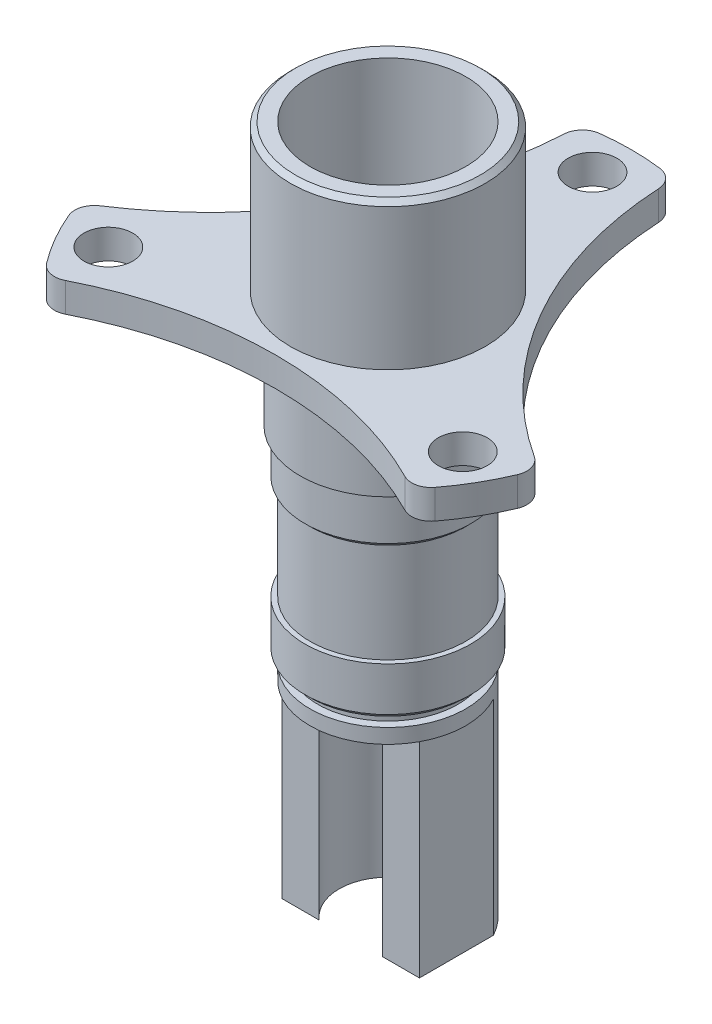
SolidWorks part; units mm, degrees
ref_plane "前视基准面" through (0, 0, 0) normal (0, 0, 1) x (1, 0, 0)
ref_plane "上视基准面" through (0, 0, 0) normal (0, 1, 0) x (1, 0, 0)
ref_plane "右视基准面" through (0, 0, 0) normal (1, 0, 0) x (0, 0, -1)
sketch "草图2" plane through (0, 0, 0) normal (0, 0, 1) x (1, 0, 0)
  line L0 (0, 0) -> (0, 49.7)
  line L1 (0, 49.7) -> (10, 49.7)
  line L3 (10, 34.7) -> (25, 34.7)
  line L4 (25, 34.7) -> (25, 31.7)
  line L5 (25, 31.7) -> (9, 31.7)
  line L9 (9, 22.7) -> (8.5, 22.7)
  line L10 (8.5, 22.7) -> (8.5, 18.2)
  line L11 (8.5, 18.2) -> (8, 18.2)
  line L12 (8, 18.2) -> (8, 7.5)
  line L13 (8, 7.5) -> (8.5, 7.5)
  line L14 (8.5, 7.5) -> (8.5, 2.5)
  line L15 (8.5, 2.5) -> (8, 2.5)
  line L17 (7.2, 1.5) -> (8, 1.5)
  line L18 (8, 1.5) -> (8, 0)
  line L19 (8, 0) -> (0, 0)
  line L20 (9, 31.7) -> (9, 22.7)
  line L21 (10, 49.7) -> (10, 34.7)
  line L23 (8, 2.5) -> (7.2, 2.5)
  line L24 (7.2, 2.5) -> (7.2, 1.5)
  dimension "D1" = 8
  dimension "D2" = 8.5
  dimension "D3" = 5
  dimension "D4" = 4.5
  dimension "D5" = 10.7
  dimension "D6" = 9
  dimension "D7" = 10
  dimension "D8" = 9
  dimension "D9" = 25
  dimension "D11" = 1.5
  dimension "D12" = 1
  dimension "D14" = 7.2
  dimension "D15" = 3
  dimension "D16" = 15
revolve "旋转1" add sketch "草图2" angle 360 about L0
sketch "草图3" plane through (0, 0, 0) normal (0, -1, 0) x (1, 0, 0)
  line L0 (-7.0399, 3.8) -> (-3.2496, 3.8)
  line L1 (3.2496, 3.8) -> (7.0399, 3.8)
  arc A0 (-7.0399, 3.8) -> (7.0399, 3.8) centre (0, 0) ccw
  arc A1 (-3.2496, 3.8) -> (3.2496, 3.8) centre (0, 0) ccw
  dimension "D1" = 16
  dimension "D2" = 10
  dimension "D3" = 3.8
extrude "凸台-拉伸1" add sketch "草图3" along normal blind 21
sketch "草图5" plane through (0, 31.7, 0) normal (0, -1, 0) x (1, 0, 0)
  line L0 (0, 50) -> (-43.3013, -25) construction
  line L1 (-43.3013, -25) -> (43.3013, -25) construction
  line L2 (43.3013, -25) -> (0, 50) construction
  line L4 (0, 0) -> (0, -25) construction
  circle A0 centre (0, 0) radius 25 construction
  arc A1 (-18.8451, 16.4275) -> (18.8451, 16.4275) centre (0, 50) ccw
  arc A2 (23.6492, 8.1066) -> (4.8041, -24.5341) centre (43.3013, -25) ccw
  arc A3 (-4.8041, -24.5341) -> (-23.6492, 8.1066) centre (-43.3013, -25) ccw
  circle A4 centre (0, 0) radius 25
  circle A5 centre (0, -21) radius 2.5
  circle A6 centre (-18.1865, 10.5) radius 2.5
  circle A7 centre (18.1865, 10.5) radius 2.5
  point P13 (0, 0)
  point P25 (0, 0)
  circle M6 centre (0, 0) radius 25
  dimension "D1" = 3
  dimension "D2" = 77
  dimension "D3" = 50
  dimension "D4" = 5
  dimension "D5" = 21
  dimension "D6" = 3
extrude "切除-拉伸1" cut sketch "草图5" against normal through all contours A3 M6 | A2 M6 | A1 M6 | A5 | A7 | A6 region at (0, 31.7, 17.9498) region at (-15.545, 31.7, -8.9749) region at (15.545, 31.7, -8.9749) region at (0, 31.7, -21) region at (-18.1865, 31.7, 10.5) region at (18.1865, 31.7, 10.5)
chamfer "倒角1" distance 0.5 angle 45 4 edges at (0, 49.7, -10) (0, 18.2, -8) (0, 31.7, -9) (0, 2.5, -8.5)
fillet "圆角1" radius 2 6 edges at (4.8041, 33.2, -24.5341) (-4.8041, 33.2, -24.5341) (23.6492, 33.2, 8.1066) (18.8451, 33.2, 16.4275) (-18.8451, 33.2, 16.4275) (-23.6492, 33.2, 8.1066)
sketch "草图8" plane through (0, 0, 0) normal (0, 0, 1) x (1, 0, 0)
  line L0 (0, 49.7) -> (0, 0)
  line L1 (9.5, 49.7) -> (-9.5, 49.7) construction
  line L7 (8, 34.7) -> (8, 49.7)
  line L8 (8, 49.7) -> (0, 49.7)
  line L9 (0, 0) -> (5, 0)
  line L10 (7.0399, 0) -> (3.2496, 0) construction
  line L11 (5, 0) -> (5, 34.7)
  line L12 (17.4287, 34.7) -> (-17.4287, 34.7) construction
  line L13 (8, 34.7) -> (5, 34.7)
  dimension "D1" = 5
  dimension "D2" = 8
revolve "切除-旋转1" cut sketch "草图8" angle 360 about L0 region at (3.1133, 27.5101, 0)
sketch "草图9" plane through (0, 0, 3.8) normal (0, 0, 1) x (1, 0, 0)
  line L0 (0, 0) -> (0, -21) construction
  line L1 (-3.2496, 0) -> (3.2496, 0) construction
  line L2 (-5, -21) -> (5, -21) construction
  circle A0 centre (0, -11.1) radius 1.5
  dimension "D1" = 3
  dimension "D2" = 9.9
extrude "切除-拉伸2" cut sketch "草图9" against normal through all
sketch "草图11" plane through (0, -21, 0) normal (0, -1, 0) x (1, 0, 0)
  line L0 (-7.0399, 3.8) -> (-7.0399, -3.8)
  line L1 (0, 0) -> (0, 5) construction
  line L2 (7.0399, 3.8) -> (7.0399, -3.8)
  circle A0 centre (0, 0) radius 8 construction
  arc A1 (3.2496, 3.8) -> (-3.2496, 3.8) centre (0, 0) ccw construction
  arc A2 (-7.0399, 3.8) -> (-7.0399, -3.8) centre (0, 0) ccw
  arc A4 (7.0399, 3.8) -> (7.0399, -3.8) centre (0, 0) cw
extrude "切除-拉伸4" cut sketch "草图11" against normal blind 21
